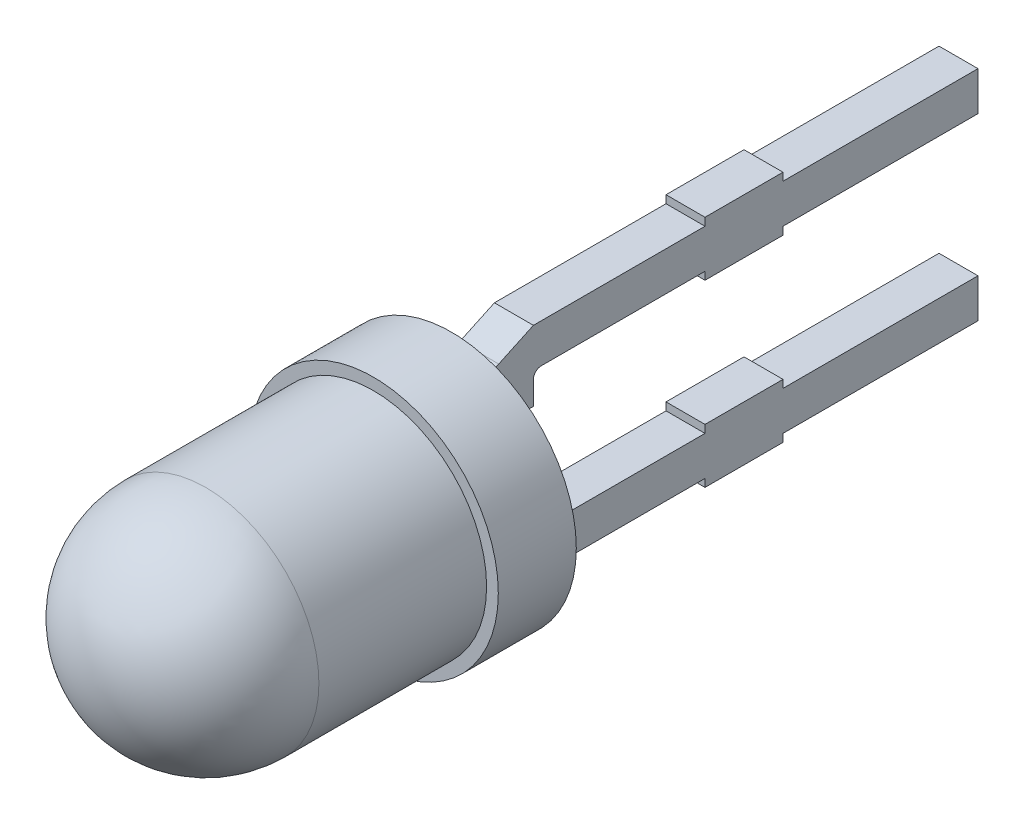
SolidWorks part; units mm, degrees
ref_plane "Front" through (0, 0, 0) normal (0, 0, 1) x (1, 0, 0)
ref_plane "Top" through (0, 0, 0) normal (0, 1, 0) x (1, 0, 0)
ref_plane "Right" through (0, 0, 0) normal (1, 0, 0) x (0, 0, -1)
sketch "Sketch1" plane through (0, 0, 0) normal (1, 0, 0) x (0, 0, -1)
  line L0 (0, 0) -> (76.2974, 0) construction
  line L1 (0, 1.45) -> (2.15, 1.45)
  line L2 (2.15, 1.45) -> (2.15, 1.6)
  line L3 (2.15, 1.6) -> (3.15, 1.6)
  line L4 (3.15, 1.6) -> (3.15, 0)
  line L5 (3.15, 0) -> (-1.45, 0)
  arc A0 (0, 1.45) -> (-1.45, 0) centre (0, 0) ccw
  dimension "D1" = 1.45
  dimension "D2" = 4.6
  dimension "D3" = 1
  dimension "D4" = 1.6
revolve "Revolve1" add sketch "Sketch1" angle 360 about L0
sketch "Sketch2" plane through (0, 0, 0) normal (1, 0, 0) x (0, 0, -1)
  line L0 (3.15, -1.6) -> (3.15, 1.6) construction
  line L1 (3.15, -1.6) -> (3.15, 1.6) construction
  line L2 (3.15, 1.027) -> (3.95, 1.4)
  line L3 (3.95, 1.4) -> (6.15, 1.4)
  line L4 (6.15, 1.4) -> (6.15, 1.5)
  line L5 (6.15, 1.5) -> (7.15, 1.5)
  line L6 (7.15, 1.5) -> (7.15, 1.4)
  line L7 (7.15, 1.4) -> (30.15, 1.4)
  line L8 (30.15, 1.4) -> (30.15, 0.9)
  line L9 (30.15, 0.9) -> (7.15, 0.9)
  line L10 (7.15, 0.9) -> (7.15, 0.8)
  line L11 (7.15, 0.8) -> (6.15, 0.8)
  line L12 (6.15, 0.8) -> (6.15, 0.9)
  line L13 (6.15, 0.9) -> (4.05, 0.9)
  line L14 (3.95, 0.8) -> (3.95, 0.5)
  line L15 (3.95, 0.5) -> (3.15, 0.5)
  line L16 (3.15, 0) -> (7.9733, 0) construction
  line L17 (3.15, 1.027) -> (3.15, 0.5)
  line L18 (3.95, -0.8) -> (3.95, -0.5)
  line L19 (6.15, -0.9) -> (4.05, -0.9)
  line L20 (6.15, -0.8) -> (6.15, -0.9)
  line L21 (7.15, -0.8) -> (6.15, -0.8)
  line L22 (7.15, -0.9) -> (7.15, -0.8)
  line L23 (30.15, -0.9) -> (7.15, -0.9)
  line L24 (30.15, -1.4) -> (30.15, -0.9)
  line L25 (7.15, -1.4) -> (30.15, -1.4)
  line L26 (7.15, -1.5) -> (7.15, -1.4)
  line L27 (6.15, -1.5) -> (7.15, -1.5)
  line L28 (6.15, -1.4) -> (6.15, -1.5)
  line L29 (3.95, -1.4) -> (6.15, -1.4)
  line L30 (3.15, -1.027) -> (3.95, -1.4)
  line L31 (3.15, -1.027) -> (3.15, -0.5)
  line L32 (3.95, -0.5) -> (3.15, -0.5)
  arc A0 (4.05, 0.9) -> (3.95, 0.8) centre (4.05, 0.8) ccw
  arc A1 (4.05, -0.9) -> (3.95, -0.8) centre (4.05, -0.8) cw
  point P19 (3.15, 0)
  dimension "D1" = 0.5
  dimension "D2" = 0.7
  dimension "D3" = 1.4
  dimension "D4" = 0.8
  dimension "D5" = 27
  dimension "D6" = 115
  dimension "D7" = 4
  dimension "D8" = 1
  dimension "D9" = 0.5
  dimension "D10" = 0.1
extrude "Extrude1" add sketch "Sketch2" along normal mid plane 0.5
fillet "Fillet1" radius 0.25 8 edges at (0, -0.5, -3.15) (0, -1.027, -3.15) (-0.25, -0.7635, -3.15) (0, 0.5, -3.15) (-0.25, 0.7635, -3.15) (0, 1.027, -3.15) (0.25, 0.7635, -3.15) (0.25, -0.7635, -3.15)
sketch "Sketch3" plane through (0, 0, 0) normal (1, 0, 0) x (0, 0, -1)
  line L0 (7.15, -1.4) -> (30.15, -1.4) construction
  line L1 (30.15, 1.4) -> (18.15, 1.4)
  line L2 (30.15, 1.4) -> (30.15, -1.4)
  line L3 (30.15, -1.4) -> (18.15, -1.4)
  line L4 (18.15, 1.4) -> (18.15, -1.4)
  line L5 (3.15, -1.6) -> (3.15, 1.6) construction
  dimension "D1" = 15
extrude "Cut-Extrude1" cut sketch "Sketch3" against normal through all both and the other way through all
sketch "Sketch4" plane through (0, 0, 0) normal (1, 0, 0) x (0, 0, -1)
  line L0 (3.15, -1.6) -> (3.15, 1.6) construction
  line L1 (9.65, 3.0595) -> (21.4981, 3.0595)
  line L2 (9.65, 3.0595) -> (9.65, -3.2798)
  line L3 (9.65, -3.2798) -> (21.4981, -3.2798)
  line L4 (21.4981, 3.0595) -> (21.4981, -3.2798)
  dimension "D1" = 6.5
extrude "Cut-Extrude2" cut sketch "Sketch4" against normal through all both and the other way through all
